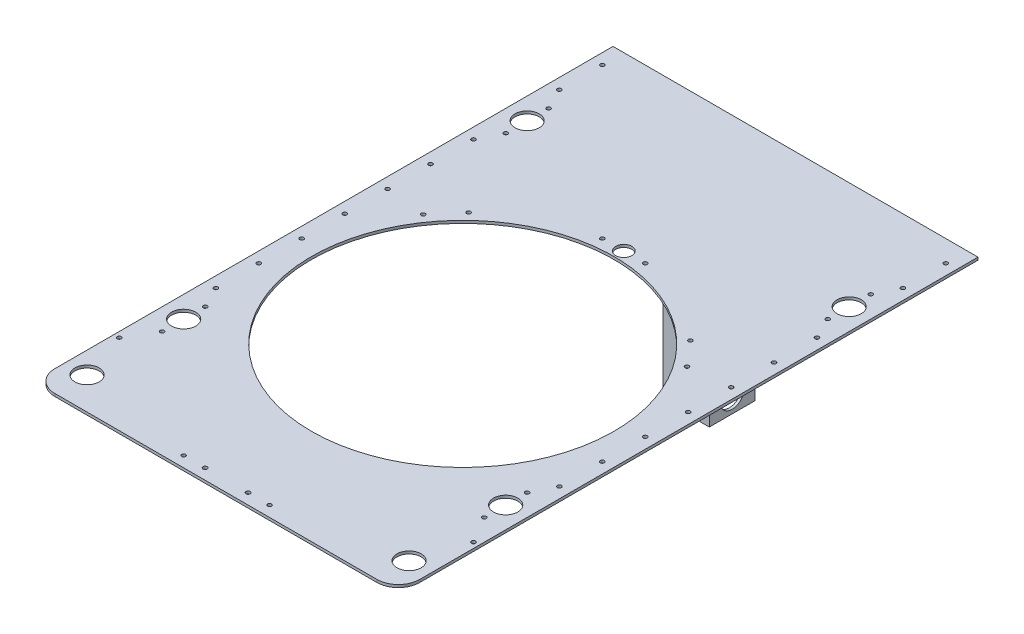
SolidWorks part; units mm, degrees
material "6063-T1"
ref_plane "Front Plane" through (0, 0, 0) normal (0, 0, 1) x (1, 0, 0)
ref_plane "Top Plane" through (0, 0, 0) normal (0, 1, 0) x (1, 0, 0)
ref_plane "Right Plane" through (0, 0, 0) normal (1, 0, 0) x (0, 0, -1)
sketch "Sketch1" plane through (0, 0, 0) normal (0, 1, 0) x (1, 0, 0)
  line L1 (-215.9, 342.9) -> (215.9, 342.9)
  line L2 (-215.9, 342.9) -> (-215.9, -342.9)
  line L3 (-215.9, -342.9) -> (215.9, -342.9)
  line L4 (215.9, 342.9) -> (215.9, -342.9)
  line L5 (-215.9, 342.9) -> (215.9, -342.9) construction
  line L6 (-215.9, -342.9) -> (215.9, 342.9) construction
  point P0 (0, 0)
  dimension "D1" = 431.8
  dimension "D2" = 685.8
extrude "Boss-Extrude1" add sketch "Sketch1" along normal blind 3.175
sketch "Sketch2" plane through (0, 3.175, 0) normal (0, 1, 0) x (1, 0, 0)
  line L0 (0, -342.9) -> (0, 342.9) construction
  line L1 (-215.9, -342.9) -> (215.9, -342.9) construction
  line L2 (215.9, 342.9) -> (-215.9, 342.9) construction
  line L3 (-215.9, 342.9) -> (-215.9, -342.9) construction
  circle A0 centre (-190.5, -304.8) radius 14.3129
  circle A1 centre (-190.5, -190.5) radius 14.3129
  circle A2 centre (190.5, -304.8) radius 14.3129
  circle A3 centre (190.5, -190.5) radius 14.3129
  circle A4 centre (190.5, -190.5) radius 25.4 construction
  circle A5 centre (-190.5, -190.5) radius 25.4 construction
  circle A6 centre (190.5, -215.9) radius 2.3813
  circle A7 centre (190.5, -165.1) radius 2.3813
  circle A8 centre (-190.5, -215.9) radius 2.3813
  circle A9 centre (-190.5, -165.1) radius 2.3813
  dimension "D1" = 28.6258
  dimension "D2" = 28.6258
  dimension "D6" = 50.8
  dimension "D7" = 50.8
  dimension "D8" = 4.7625
  dimension "D9" = 4.7625
  dimension "D10" = 4.7625
  dimension "D11" = 4.7625
  dimension "D3" = 38.1
  dimension "D4" = 114.3
  dimension "D5" = 25.4
extrude "Cut-Extrude1" cut sketch "Sketch2" against normal through all
sketch "Sketch3" plane through (0, 0, 0) normal (0, -1, 0) x (-1, 0, 0)
  line L1 (29.8706, 270.2084) -> (-24.7394, 270.2084)
  line L2 (29.8706, 270.2084) -> (29.8706, 216.2334)
  line L3 (29.8706, 216.2334) -> (-24.7394, 216.2334)
  line L4 (-24.7394, 270.2084) -> (-24.7394, 216.2334)
  line L5 (29.8706, 270.2084) -> (-24.7394, 216.2334) construction
  line L6 (29.8706, 216.2334) -> (-24.7394, 270.2084) construction
  point P0 (2.5656, 243.2209)
  dimension "D1" = 53.975
  dimension "D2" = 54.61
extrude "Boss-Extrude2" add sketch "Sketch3" along normal blind 203.2
fillet "Fillet1" radius 20.32 4 edges at (24.7394, 0, -243.2209) (-2.5656, 0, -270.2084) (-2.5656, 0, -216.2334) (-29.8706, 0, -243.2209)
sketch "Sketch4" plane through (0, -203.2, 0) normal (0, -1, 0) x (-1, 0, 0)
  line L0 (-24.7394, 216.2334) -> (29.8706, 216.2334) construction
  line L1 (26.6956, 267.0334) -> (-21.5644, 267.0334)
  line L2 (26.6956, 267.0334) -> (26.6956, 219.4084)
  line L3 (26.6956, 219.4084) -> (-21.5644, 219.4084)
  line L4 (-21.5644, 267.0334) -> (-21.5644, 219.4084)
  line L5 (26.6956, 267.0334) -> (-21.5644, 219.4084) construction
  line L6 (26.6956, 219.4084) -> (-21.5644, 267.0334) construction
  line L7 (29.8706, 270.2084) -> (-24.7394, 270.2084) construction
  line L8 (29.8706, 216.2334) -> (29.8706, 270.2084) construction
  line L9 (-24.7394, 270.2084) -> (-24.7394, 216.2334) construction
  point P0 (2.5656, 243.2209)
  dimension "D1" = 3.175
  dimension "D2" = 3.175
  dimension "D3" = 3.175
  dimension "D4" = 3.175
extrude "Cut-Extrude2" cut sketch "Sketch4" against normal blind 203.2
sketch "Sketch5" plane through (-29.8706, 0, 0) normal (-1, 0, 0) x (0, 0, 1)
  line L0 (-216.2334, -203.2) -> (-216.2334, -20.32) construction
  line L1 (-216.2334, -203.2) -> (-270.2084, -203.2) construction
  circle A0 centre (-243.2209, -184.15) radius 14.2875
  dimension "D1" = 28.575
  dimension "D2" = 26.9875
  dimension "D3" = 19.05
extrude "Cut-Extrude3" cut sketch "Sketch5" against normal blind 203.2
sketch "Sketch6" plane through (0, 3.175, 0) normal (0, 1, 0) x (1, 0, 0)
  circle A0 centre (0, -50.8) radius 179.07
  dimension "D1" = 358.14
  dimension "D2" = 50.8
extrude "Cut-Extrude4" cut sketch "Sketch6" against normal through all
sketch "Sketch8" plane through (0, 3.175, 0) normal (0, 1, 0) x (1, 0, 0)
  circle A0 centre (0, 139.7) radius 9.525
  circle A2 centre (0, 139.7) radius 25.4 construction
  circle A3 centre (25.4, 139.7) radius 2.3813
  circle A4 centre (-25.4, 139.7) radius 2.3813
  dimension "D1" = 19.05
  dimension "D3" = 50.8
  dimension "D4" = 4.7625
  dimension "D5" = 4.7625
  dimension "D2" = 139.7
extrude "Cut-Extrude6" cut sketch "Sketch8" against normal through all
fillet "Fillet2" radius 25.4 2 edges at (215.9, 1.5875, 342.9) (-215.9, 1.5875, 342.9)
sketch "Sketch10" plane through (0, 3.175, 0) normal (0, 1, 0) x (1, 0, 0)
  line L0 (-215.9, 342.9) -> (-215.9, -317.5) construction
  line L1 (215.9, -317.5) -> (215.9, 342.9) construction
  circle A0 centre (-190.5, 215.9) radius 14.3129
  circle A1 centre (190.5, 215.9) radius 14.3129
  circle A2 centre (-190.5, 215.9) radius 25.4 construction
  circle A3 centre (190.5, 215.9) radius 25.4 construction
  circle A4 centre (190.5, 190.5) radius 2.3813
  circle A5 centre (190.5, 241.3) radius 2.3813
  circle A6 centre (-190.5, 190.5) radius 2.3813
  circle A7 centre (-190.5, 241.3) radius 2.3813
  circle A8 centre (190.5, -190.5) radius 14.3129 construction
  circle A9 centre (-190.5, -190.5) radius 14.3129 construction
  dimension "D1" = 28.6258
  dimension "D2" = 50.8
  dimension "D3" = 28.6258
  dimension "D4" = 50.8
  dimension "D5" = 4.7625
  dimension "D6" = 4.7625
  dimension "D7" = 4.7625
  dimension "D8" = 4.7625
  dimension "D9" = 25.4
  dimension "D10" = 25.4
  dimension "D11" = 406.4
  dimension "D12" = 406.4
extrude "Cut-Extrude8" cut sketch "Sketch10" against normal through all
sketch "Sketch11" plane through (0, 3.175, 0) normal (0, 1, 0) x (1, 0, 0)
  line L0 (0, -50.8) -> (156.0485, 58.4663) construction
  line L6 (0, 0) -> (0, 139.7) construction
  circle A0 centre (0, -50.8) radius 179.07
  circle A1 centre (0, -50.8) radius 179.07 construction
  circle A2 centre (0, -50.8) radius 184.15
  circle A3 centre (0, -50.8) radius 215.9
  circle A4 centre (156.0485, 58.4663) radius 2.3813
  circle A5 centre (131.1838, 87.3342) radius 2.3813
  circle A6 centre (0, -50.8) radius 190.5 construction
  circle A7 centre (-131.1838, 87.3342) radius 2.3813
  circle A8 centre (-156.0485, 58.4663) radius 2.3813
  dimension "D1" = 368.3
  dimension "D6" = 431.8
  dimension "D7" = 381
  dimension "D9" = 4.7625
  dimension "D10" = 4.7625
  dimension "D2" = 55
  dimension "D8" = 38.1
extrude "Cut-Extrude9" cut sketch "Sketch11" against normal through all contours A4 | A5 | A7 | A8 region at (156.0485, 3.175, -58.4663) region at (131.1838, 3.175, -87.3342) region at (-131.1838, 3.175, -87.3342) region at (-156.0485, 3.175, -58.4663)
sketch "Sketch13" plane through (0, 3.175, 0) normal (0, 1, 0) x (1, 0, 0)
  line L0 (-215.9, 342.9) -> (-215.9, -317.5) construction
  line L1 (215.9, 342.9) -> (-215.9, 342.9) construction
  line L2 (0, -342.9) -> (0, 342.9) construction
  line L3 (-190.5, -342.9) -> (190.5, -342.9) construction
  circle A0 centre (-203.2, 317.5) radius 2.3813
  circle A1 centre (-203.2, 266.7) radius 2.3813
  circle A2 centre (-203.2, 215.9) radius 2.3813 [skipped]
  circle A3 centre (-203.2, 165.1) radius 2.3813
  circle A4 centre (-203.2, 114.3) radius 2.3813
  circle A5 centre (-203.2, 63.5) radius 2.3813
  circle A6 centre (-203.2, 12.7) radius 2.3813
  circle A7 centre (-203.2, -38.1) radius 2.3813
  circle A8 centre (-203.2, -88.9) radius 2.3813
  circle A9 centre (-203.2, -139.7) radius 2.3813
  circle A10 centre (203.2, -139.7) radius 2.3813
  circle A11 centre (203.2, 12.7) radius 2.3813
  circle A12 centre (203.2, 63.5) radius 2.3813
  circle A13 centre (203.2, 114.3) radius 2.3813
  circle A14 centre (203.2, 165.1) radius 2.3813
  circle A15 centre (203.2, 266.7) radius 2.3813
  circle A16 centre (203.2, 317.5) radius 2.3813
  circle A17 centre (-25.4, -330.2) radius 2.4664
  circle A20 centre (-50.8, -330.2) radius 2.3078
  circle A21 centre (50.8, -330.2) radius 2.3078
  circle A22 centre (25.4, -330.2) radius 2.4664
  circle A23 centre (203.2, -88.9) radius 2.3813
  circle A24 centre (203.2, -38.1) radius 2.3813
  dimension "D1" = 4.7625
  dimension "D2" = 12.7
  dimension "D3" = 25.4
  dimension "D5" = 25.4
  dimension "D6" = 50.8
  dimension "D7" = 12.7
  dimension "D8" = 12.7
  dimension "D4" = 10
extrude "Cut-Extrude10" cut sketch "Sketch13" against normal through all
sketch "Sketch14" plane through (0, 3.175, 0) normal (0, 1, 0) x (1, 0, 0)
  line L0 (215.9, -317.5) -> (215.9, 342.9) construction
  line L1 (0, -342.9) -> (0, -229.87) construction
  line L2 (-190.5, -342.9) -> (190.5, -342.9) construction
  circle A0 centre (209.55, -247.65) radius 2.3813
  circle A1 centre (190.5, -304.8) radius 14.3129 construction
  circle A2 centre (0, -50.8) radius 179.07 construction
  circle A3 centre (-209.55, -247.65) radius 2.3813
  dimension "D1" = 57.15
  dimension "D3" = 4.7625
  dimension "D2" = 6.35
extrude "Cut-Extrude11" cut sketch "Sketch14" against normal through all
